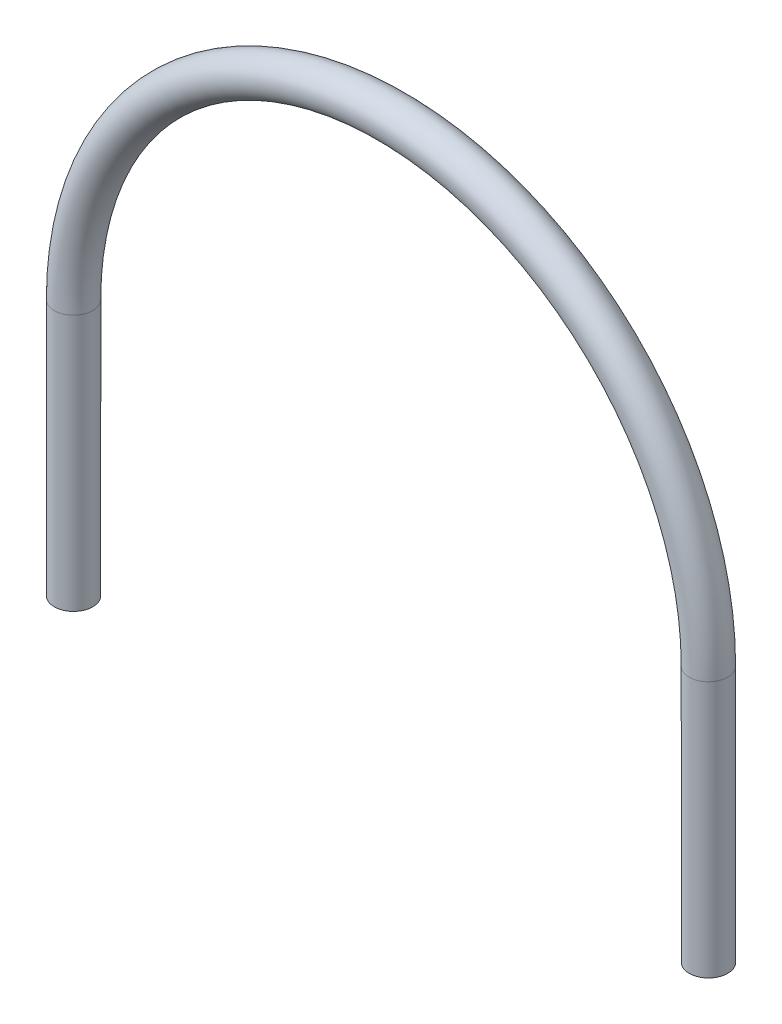
SolidWorks part; units mm, degrees
ref_plane "Plano frontal" through (0, 0, 0) normal (0, 0, 1) x (1, 0, 0)
ref_plane "Plano superior" through (0, 0, 0) normal (0, 1, 0) x (1, 0, 0)
ref_plane "Plano direito" through (0, 0, 0) normal (1, 0, 0) x (0, 0, -1)
sketch "Sketch1" plane through (0, 0, 0) normal (0, 0, 1) x (1, 0, 0)
  line L0 (-476.3838, 0) -> (513.6162, 0) construction
  line L1 (-476.3838, 0) -> (-476.3838, -400)
  line L2 (513.6162, 0) -> (513.6162, -400)
  arc A0 (-476.3838, 0) -> (513.6162, 0) centre (18.6162, 0) cw
  dimension "D1" = 495
  dimension "D2" = 400
sweep "Sweep-Thin1" add path "Sketch1" circular profile diameter 60 parameters "D1"=3, "D3"=60
